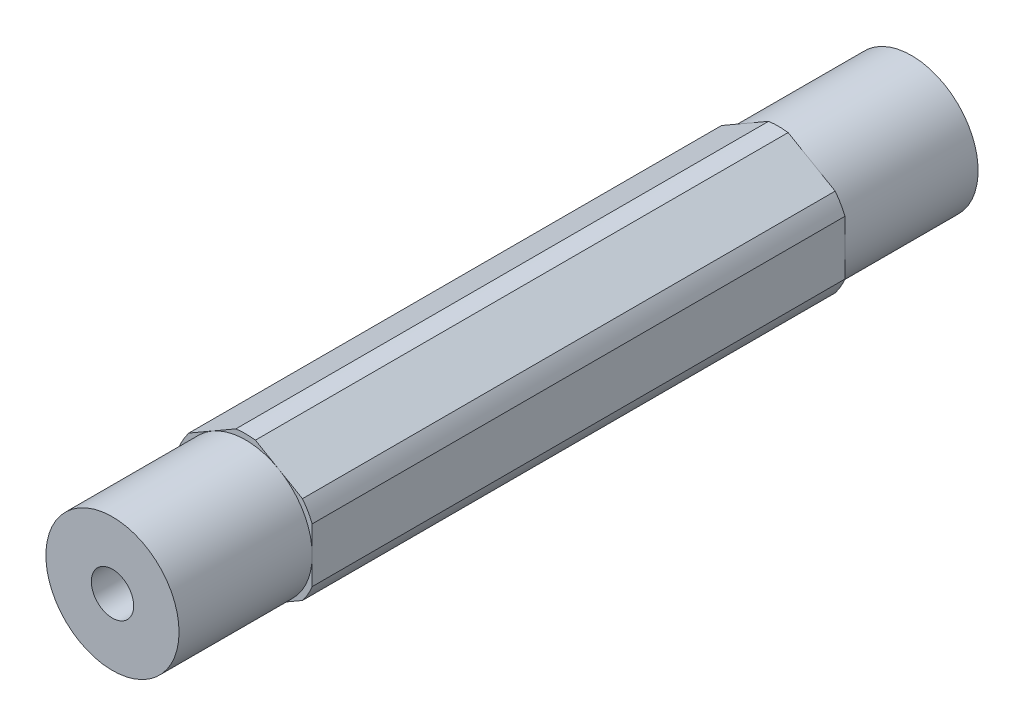
SolidWorks part; units mm, degrees
other "Markup1"
sketch "Sketch3" plane through (6.35, 7.3323, -19.05) normal (0.3384, 0.0641, -0.9388) x (-0.9259, -0.1556, -0.3443)
ref_plane "Front Plane" through (0, 0, 0) normal (0, 0, 1) x (1, 0, 0)
ref_plane "Top Plane" through (0, 0, 0) normal (0, 1, 0) x (1, 0, 0)
ref_plane "Right Plane" through (0, 0, 0) normal (1, 0, 0) x (0, 0, -1)
sketch "Sketch1" plane through (0, 0, 0) normal (0, 0, 1) x (1, 0, 0)
  line L1 (0, 7.3323) -> (-6.35, 3.6662)
  line L2 (-6.35, 3.6662) -> (-6.35, -3.6662)
  line L3 (-6.35, -3.6662) -> (0, -7.3323)
  line L4 (0, -7.3323) -> (6.35, -3.6662)
  line L5 (6.35, -3.6662) -> (6.35, 3.6662)
  line L6 (6.35, 3.6662) -> (0, 7.3323)
  circle A0 centre (0, 0) radius 6.35 construction
  dimension "D1" = 12.7
extrude "Boss-Extrude1" add sketch "Sketch1" along normal mid plane 76.2
sketch "Sketch2" plane through (0, 0, -38.1) normal (0, 0, -1) x (-1, 0, 0)
  circle A0 centre (0, 0) radius 2.0193
  dimension "D1" = 4.0386
extrude "Cut-Extrude1" cut sketch "Sketch2" against normal through all
sketch "Sketch4" plane through (0, 0, -38.1) normal (0, 0, -1) x (-1, 0, 0)
  circle A0 centre (0, 0) radius 6.858
  circle A1 centre (0, 0) radius 7.3323
  dimension "D1" = 13.716
extrude "Cut-Extrude2" cut sketch "Sketch4" against normal through all
sketch "Sketch5" plane through (0, 0, -38.1) normal (0, 0, -1) x (-1, 0, 0)
  circle A0 centre (0, 0) radius 6.35
  circle A1 centre (0, 0) radius 6.858
  arc A2 (0.9317, 6.7944) -> (-0.9317, 6.7944) centre (0, 0) ccw construction
  dimension "D1" = 12.7
extrude "Cut-Extrude3" cut sketch "Sketch5" against normal blind 12.7
sketch "Sketch6" plane through (0, 0, 38.1) normal (0, 0, 1) x (1, 0, 0)
  circle A0 centre (0, 0) radius 6.858
  circle A1 centre (0, 0) radius 6.35
  arc A2 (0.9317, 6.7944) -> (-0.9317, 6.7944) centre (0, 0) ccw construction
  dimension "D1" = 12.7
extrude "Cut-Extrude4" cut sketch "Sketch6" against normal blind 12.7
